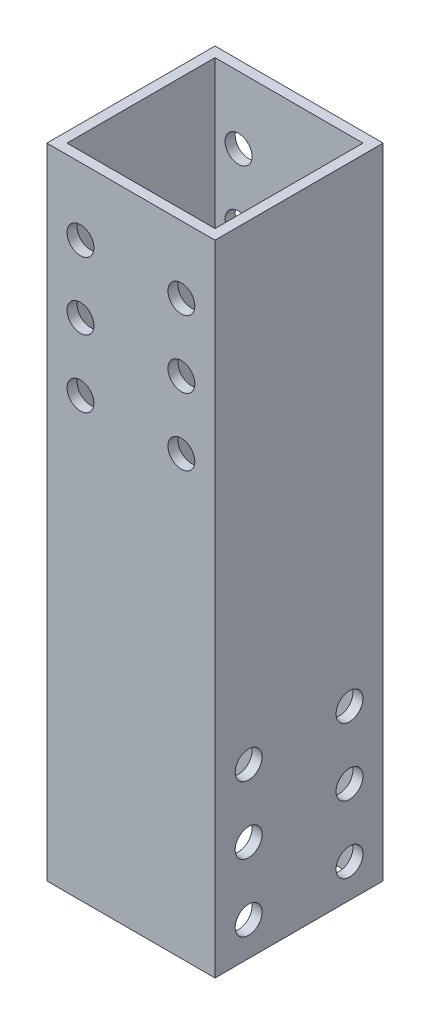
SolidWorks part; units mm, degrees
material "1060 Alloy"
ref_plane "Front Plane" through (0, 0, 0) normal (0, 0, 1) x (1, 0, 0)
ref_plane "Top Plane" through (0, 0, 0) normal (0, 1, 0) x (1, 0, 0)
ref_plane "Right Plane" through (0, 0, 0) normal (1, 0, 0) x (0, 0, -1)
sketch "Sketch3" plane through (0, 0, 0) normal (0, 1, 0) x (1, 0, 0)
  line L0 (0, 86.7063) -> (0, -87.1032) construction
  line L1 (-136.9048, 0) -> (130.9524, 0) construction
  line L7 (-12.5, 12.5) -> (12.5, 12.5)
  line L8 (-12.5, 12.5) -> (-12.5, -12.5)
  line L13 (-12.5, -12.5) -> (12.5, -12.5)
  line L14 (12.5, 12.5) -> (12.5, -12.5)
  line L15 (-12.5, 12.5) -> (12.5, -12.5) construction
  line L16 (-12.5, -12.5) -> (12.5, 12.5) construction
  line L17 (-11, 11) -> (11, 11)
  line L18 (-11, 11) -> (-11, -11)
  line L19 (-11, -11) -> (11, -11)
  line L20 (11, 11) -> (11, -11)
  line L21 (-11, 11) -> (11, -11) construction
  line L22 (-11, -11) -> (11, 11) construction
  point P5 (0, 0)
  point P10 (0, 0)
  dimension "D1" = 25
  dimension "D2" = 25
  dimension "D3" = 22
extrude "Boss-Extrude1" add sketch "Sketch3" along normal blind 47.5 and the other way blind 47.5
sketch "Sketch6" plane through (12.5, 0, 0) normal (1, 0, 0) x (0, 0, -1)
  line L0 (0, 0) -> (0, -102.9817) construction
  line L1 (-12.5, -47.5) -> (12.5, -47.5) construction
  circle A0 centre (7.5, -42.5) radius 2
  circle A1 centre (7.5, -22.5) radius 2
  circle A3 centre (-7.5, -42.5) radius 2
  circle A4 centre (-7.5, -22.5) radius 2
  circle A5 centre (7.5, -32.5) radius 2
  circle A6 centre (-7.5, -32.5) radius 2
  dimension "D2" = 10
  dimension "D9" = 10
  dimension "D3" = 7.5
  dimension "D4" = 7.5
  dimension "D5" = 7.5
  dimension "D6" = 7.5
  dimension "D7" = 5
  dimension "D8" = 10
  dimension "D10" = 5
  dimension "D11" = 10
  dimension "D12" = 7.5
  dimension "D13" = 7.5
extrude "Cut-Extrude3" cut sketch "Sketch6" against normal blind 25
sketch "Sketch7" plane through (0, 0, -12.5) normal (0, 0, -1) x (-1, 0, 0)
  line L0 (0, 0) -> (0, 70.1061) construction
  line L2 (-12.5, 47.5) -> (12.5, 47.5) construction
  circle A0 centre (7.5, 37.5) radius 2
  circle A1 centre (7.5, 27.5) radius 2
  circle A3 centre (-7.5, 37.5) radius 2
  circle A4 centre (-7.5, 27.5) radius 2
  circle A5 centre (-7.5, 17.5) radius 2
  circle A6 centre (7.5, 17.5) radius 2
  dimension "D1" = 7.5
  dimension "D5" = 10
  dimension "D2" = 7.5
  dimension "D3" = 7.5
  dimension "D4" = 7.5
  dimension "D6" = 10
  dimension "D7" = 10
  dimension "D8" = 10
  dimension "D9" = 7.5
  dimension "D10" = 10
  dimension "D11" = 7.5
  dimension "D12" = 10
extrude "Cut-Extrude4" cut sketch "Sketch7" against normal blind 25
